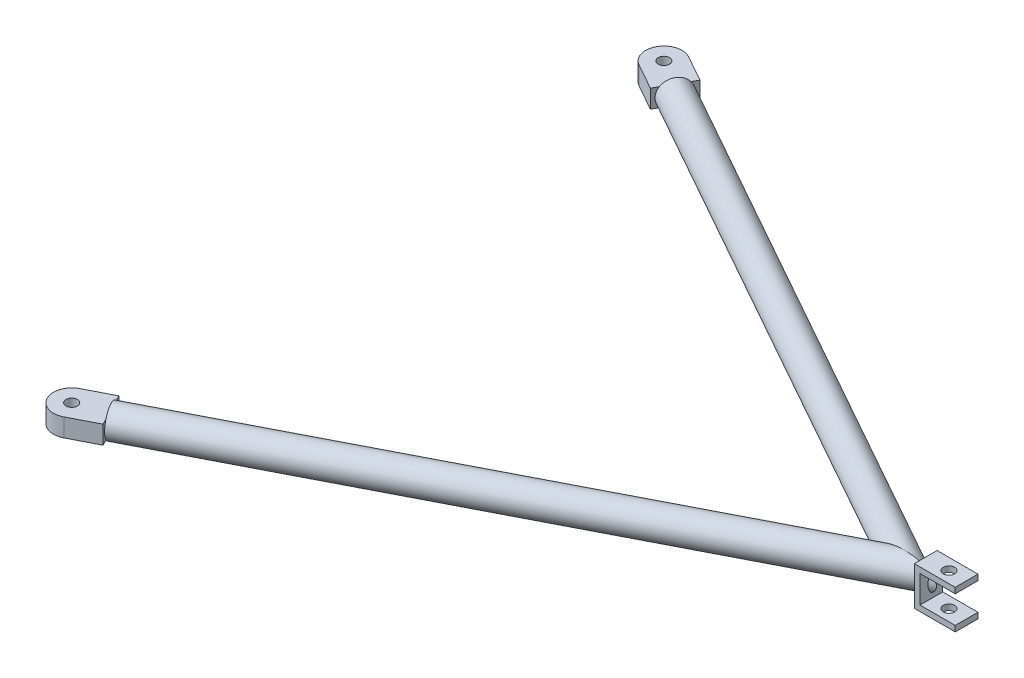
SolidWorks part; units mm, degrees
ref_plane "Front Plane" through (0, 0, 0) normal (0, 0, 1) x (1, 0, 0)
ref_plane "Top Plane" through (0, 0, 0) normal (0, 1, 0) x (1, 0, 0)
ref_plane "Right Plane" through (0, 0, 0) normal (1, 0, 0) x (0, 0, -1)
sketch "Sketch1" plane through (0, 0, 0) normal (0, 1, 0) x (1, 0, 0)
  line L0 (-307.2634, -157.8543) -> (0, 0)
  line L1 (0, 0) -> (-307.2634, 172.3457)
  line L2 (-307.2634, 172.3457) -> (-307.2634, -157.8543) construction
  dimension "D1" = 345.44
  dimension "D2" = 352.298
  dimension "D3" = 330.2
ref_plane "Plane1" through (-307.2634, 0, 157.8543) normal (0.8895, 0, -0.457) x (-0.457, 0, -0.8895)
sketch "Sketch2" plane through (-307.2634, 0, 157.8543) normal (0.8895, 0, -0.457) x (-0.457, 0, -0.8895)
  circle A0 centre (0, 0) radius 8.255
  dimension "D1" = 16.51
sweep "Sweep1" add profiles "Sketch2" path "Sketch1"
sketch "Sketch3" plane through (0, 0, 0) normal (0, 0, 1) x (1, 0, 0)
  line L0 (33.9318, 10.795) -> (11.0934, 10.795)
  line L1 (11.0934, 10.795) -> (11.0934, -10.795)
  line L2 (11.0934, -10.795) -> (33.9318, -10.795)
  line L3 (33.9318, -10.795) -> (33.9318, -7.62)
  line L4 (33.9318, -7.62) -> (14.2684, -7.62)
  line L5 (14.2684, -7.62) -> (14.2684, 7.62)
  line L6 (14.2684, 7.62) -> (33.9318, 7.62)
  line L7 (33.9318, 7.62) -> (33.9318, 10.795)
  line L8 (17.4434, 0) -> (-17.4435, 0) construction
  ellipse E0 centre (0, 0) end of major axis (17.4434, 0) minor radius 8.255 construction
  ellipse E1 centre (0, 0) end of major axis (17.4434, 0) minor radius 8.255 construction
  point P21 (11.0934, 0)
  dimension "D1" = 3.175
  dimension "D2" = 15.24
  dimension "D3" = 3.175
  dimension "D4" = 6.35
extrude "Boss-Extrude1" add sketch "Sketch3" along normal blind 6.35 and the other way blind 6.35
sketch "Sketch4" plane through (-307.2634, 0, 157.8543) normal (-0.8895, 0, 0.457) x (0.457, 0, 0.8895)
  line L1 (-10.16, 5.08) -> (10.16, 5.08)
  line L2 (-10.16, 5.08) -> (-10.16, -5.08)
  line L3 (-10.16, -5.08) -> (10.16, -5.08)
  line L4 (10.16, 5.08) -> (10.16, -5.08)
  line L5 (-10.16, 5.08) -> (10.16, -5.08) construction
  line L6 (-10.16, -5.08) -> (10.16, 5.08) construction
  circle A1 centre (0, 0) radius 8.255
  circle A2 centre (0, 0) radius 8.255 construction
  dimension "D2" = 20.32
  dimension "D3" = 10.16
  dimension "D1" = 0
extrude "Boss-Extrude2" add sketch "Sketch4" along normal blind 10.16 and the other way blind 16.256
sketch "Sketch5" plane through (-307.2634, 0, -172.3457) normal (-0.8722, 0, -0.4892) x (-0.4892, 0, 0.8722)
  line L1 (-10.16, 5.08) -> (10.16, 5.08)
  line L2 (-10.16, 5.08) -> (-10.16, -5.08)
  line L3 (-10.16, -5.08) -> (10.16, -5.08)
  line L4 (10.16, 5.08) -> (10.16, -5.08)
  line L5 (-10.16, 5.08) -> (10.16, -5.08) construction
  line L6 (-10.16, -5.08) -> (10.16, 5.08) construction
  point P0 (0, 0)
  dimension "D1" = 20.32
  dimension "D2" = 10.16
extrude "Boss-Extrude3" add sketch "Sketch5" along normal blind 10.16 and the other way blind 16.51
sketch "Sketch6" plane through (0, 5.08, 0) normal (0, 1, 0) x (1, 0, 0)
  line L0 (-287.8936, 173.1302) -> (-311.1544, 186.1773) construction
  line L1 (-297.8343, 155.4077) -> (-321.095, 168.4548) construction
  line L2 (-321.095, 168.4548) -> (-311.1544, 186.1773) construction
  line L3 (-312.2338, 163.4845) -> (-321.095, 168.4548)
  line L4 (-321.095, 168.4548) -> (-316.1247, 177.3161)
  arc A0 (-316.1247, 177.3161) -> (-312.2338, 163.4845) centre (-307.2634, 172.3457) ccw
extrude "Cut-Extrude1" cut sketch "Sketch6" against normal through all
ref_plane "Plane2" through (0, 0, 0) normal (-0.4892, 0, 0.8722) x (0.8722, 0, 0.4892)
ref_plane "Plane3" through (0, 0, 0) normal (0.457, 0, 0.8895) x (0.8895, 0, -0.457)
mirror "Mirror1" about plane through (0, 0, 0) normal (-0.4892, 0, 0.8722) of "Cut-Extrude1"
sketch "Sketch7" plane through (0, 5.08, 0) normal (0, 1, 0) x (1, 0, 0)
  line L0 (-288.1612, -159.463) -> (-311.6578, -171.5342) construction
  line L1 (-297.4468, -141.3887) -> (-320.9434, -153.4599) construction
  line L2 (-311.6578, -171.5342) -> (-320.9434, -153.4599) construction
  line L3 (-302.6207, -166.8914) -> (-311.6578, -171.5342)
  line L4 (-311.6578, -171.5342) -> (-316.3006, -162.497)
  arc A0 (-302.6207, -166.8914) -> (-316.3006, -162.497) centre (-307.2634, -157.8543) cw
extrude "Cut-Extrude2" cut sketch "Sketch7" against normal through all
mirror "Mirror2" about plane through (0, 0, 0) normal (0.457, 0, 0.8895) of "Cut-Extrude2"
sketch "Sketch8" plane through (-307.2634, 0, 157.8543) normal (-0.8895, 0, 0.457) x (0.457, 0, 0.8895)
  line L0 (6.5068, -5.08) -> (-6.5068, -5.08) construction
  line L1 (-6.5068, 5.08) -> (6.5068, 5.08) construction
  line L2 (6.5068, -5.08) -> (-6.5068, -5.08)
  line L3 (-6.5068, 5.08) -> (6.5068, 5.08)
  arc A0 (-6.5068, -5.08) -> (6.5068, -5.08) centre (0, 0) ccw construction
  arc A1 (6.5068, 5.08) -> (-6.5068, 5.08) centre (0, 0) ccw construction
  arc A2 (-6.5068, -5.08) -> (6.5068, -5.08) centre (0, 0) ccw
  arc A3 (6.5068, 5.08) -> (-6.5068, 5.08) centre (0, 0) ccw
extrude "Cut-Extrude3" cut sketch "Sketch8" against normal up to surface (16.256 mm away) up to face at (-288.7962, 0, 158.227)
sketch "Sketch9" plane through (-307.2634, 0, -172.3457) normal (-0.8722, 0, -0.4892) x (-0.4892, 0, 0.8722)
  line L0 (6.5068, -5.08) -> (-6.5068, -5.08) construction
  line L1 (-6.5068, 5.08) -> (6.5068, 5.08) construction
  line L2 (6.5068, -5.08) -> (-6.5068, -5.08)
  line L3 (-6.5068, 5.08) -> (6.5068, 5.08)
  arc A0 (-6.5068, -5.08) -> (6.5068, -5.08) centre (0, 0) ccw construction
  arc A1 (6.5068, 5.08) -> (-6.5068, 5.08) centre (0, 0) ccw construction
  arc A2 (-6.5068, -5.08) -> (6.5068, -5.08) centre (0, 0) ccw
  arc A3 (6.5068, 5.08) -> (-6.5068, 5.08) centre (0, 0) ccw
extrude "Cut-Extrude4" cut sketch "Sketch9" against normal up to surface (16.51 mm away) up to face at (-297.1545, 0, -156.6197)
sketch "Sketch10" plane through (0, 5.08, 0) normal (0, 1, 0) x (1, 0, 0)
  point P0 (-307.2634, 172.3457)
  point P1 (-307.2634, -157.8543)
hole_wizard "E (0.25) Diameter Hole1" positions "3DSketch1" profile "Sketch11" hole size "E" standard "ANSI Inch"
sketch3d "3DSketch1"
  point P0 (-307.2634, 5.08, -172.3457)
  point P3 (-307.2634, 5.08, 157.8543)
sketch "Sketch11" plane through (-307.2634, 5.08, -172.3457) normal (1, 0, 0) x (0, 0, 1)
  line L0 (0, 0) -> (0, 20.9577)
  line L1 (0, 20.9577) -> (3.175, 19.05)
  line L2 (3.175, 19.05) -> (3.175, 0)
  line L5 (3.175, 0) -> (0, 0)
  line L10 (0, 20.9577) -> (-3.175, 19.05) construction
  line L11 (0, -6.35) -> (0, 107.95) construction
  dimension "Hole Dia." = 6.35
  dimension "Hole Depth" = 19.05
  dimension "Drill Angle" = 118
sketch "Sketch13" plane through (0, -7.62, 0) normal (0, 1, 0) x (1, 0, 0)
  line L0 (14.2684, 6.35) -> (33.9318, -6.35) construction
  line L1 (33.9318, 6.35) -> (14.2684, -6.35) construction
  line L4 (14.2684, 6.35) -> (14.2684, -6.35)
  line L5 (14.2684, -6.35) -> (33.9318, -6.35)
  line L6 (33.9318, -6.35) -> (33.9318, 6.35)
  line L7 (33.9318, 6.35) -> (14.2684, 6.35)
  line L8 (14.2684, 6.35) -> (14.2684, -6.35) construction
  line L9 (14.2684, -6.35) -> (33.9318, -6.35) construction
  line L10 (33.9318, -6.35) -> (33.9318, 6.35) construction
  line L11 (33.9318, 6.35) -> (14.2684, 6.35) construction
  circle A0 centre (24.1001, 0) radius 3.175
  dimension "D2" = 6.35
  dimension "D1" = 0
extrude "Cut-Extrude5" cut sketch "Sketch13" against normal through all both and the other way through all
ref_point "Point1"
ref_point "Point2"
sketch3d "3DSketch2"
  line L0 (24.1001, 10.795, 0) -> (24.1001, -10.795, 0)
  circle A0 centre (24.1001, -10.795, 0) radius 3.175 construction
  circle A1 centre (24.1001, 10.795, 0) radius 3.175 construction
  circle A2 centre (24.1001, -10.795, 0) radius 3.175
  circle A3 centre (24.1001, 10.795, 0) radius 3.175
  point P2 (24.1001, -7.62, 0)
  point P5 (24.1001, 13.97, 0)
  point P7 (24.1001, -7.62, 0)
  point P9 (24.1001, 13.97, 0)
  point P10 (24.1001, 0, 0)
ref_point "JOINT"
